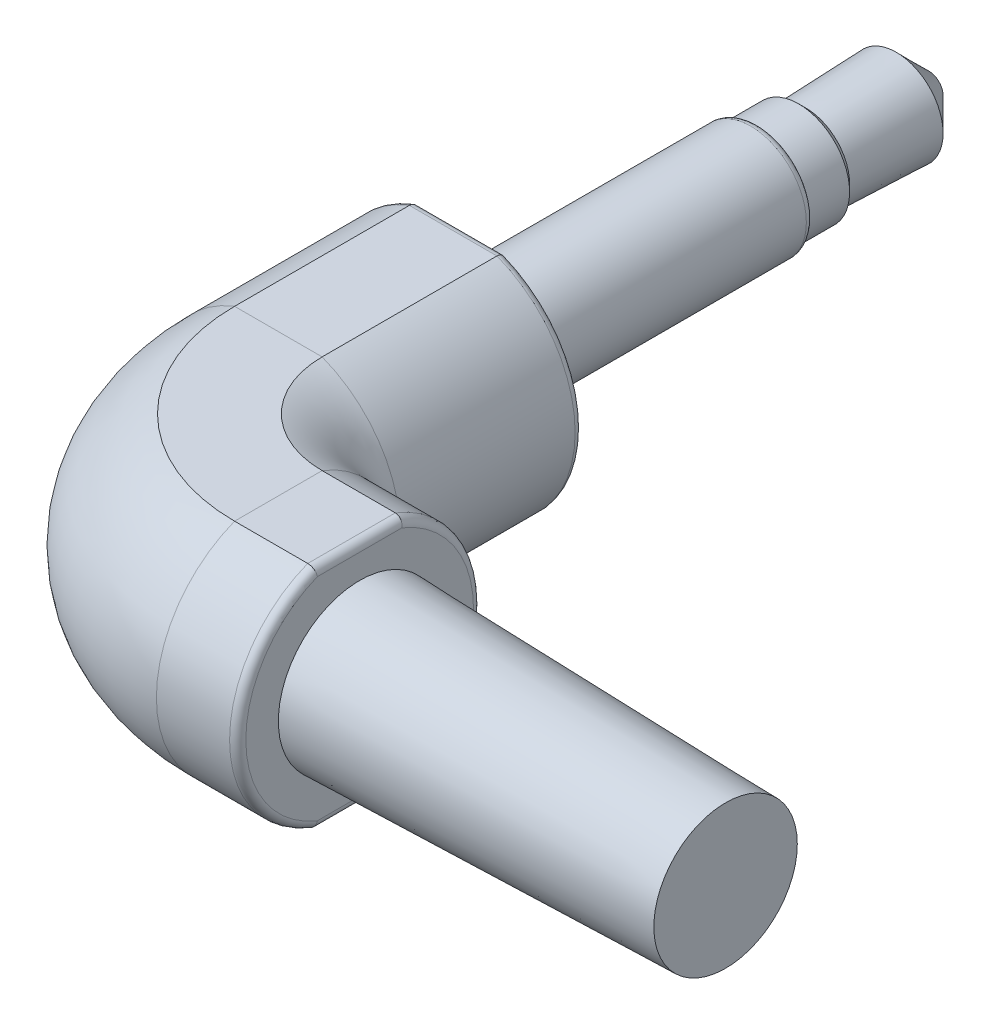
SolidWorks part; units mm, degrees
ref_plane "Front Plane" through (0, 0, 0) normal (0, 0, 1) x (1, 0, 0)
ref_plane "Top Plane" through (0, 0, 0) normal (0, 1, 0) x (1, 0, 0)
ref_plane "Right Plane" through (0, 0, 0) normal (1, 0, 0) x (0, 0, -1)
sketch "Sketch1" plane through (0, 0, 0) normal (0, 0, 1) x (1, 0, 0)
  circle A0 centre (0, 0) radius 1.4605
  dimension "D1" = 2.921
extrude "Boss-Extrude1" add sketch "Sketch1" against normal blind 14.605
chamfer "Chamfer1" distance 1.016 angle 45 1 edges at (1.4605, 0, -14.605)
sketch "Sketch4" plane through (0, 0, 0) normal (0, 1, 0) x (1, 0, 0)
  line L0 (1.4605, 13.589) -> (0.986, 0)
  line L1 (-1.4605, 0) -> (1.4605, 0) construction
  line L2 (0.986, 0) -> (2.0403, 0)
  line L3 (2.0403, 0) -> (2.0403, 13.589)
  line L4 (2.0403, 13.589) -> (1.4605, 13.589)
  line L5 (0, -1000) -> (0, 49000) construction
  dimension "D1" = 88
revolve "Cut-Revolve1" cut sketch "Sketch4" angle 360 about L5
sketch "Sketch2" plane through (0, 0, 0) normal (0, 0, 1) x (1, 0, 0)
  circle A0 centre (0, 0) radius 1.5875
  dimension "D1" = 3.175
extrude "Boss-Extrude2" add sketch "Sketch2" against normal blind 10.795
chamfer "Chamfer2" distance 0.254 angle 45 1 edges at (1.5875, 0, -10.795)
sketch "Sketch3" plane through (0, 0, 0) normal (0, 0, 1) x (1, 0, 0)
  circle A0 centre (0, 0) radius 1.7399
  dimension "D1" = 3.4798
extrude "Boss-Extrude3" add sketch "Sketch3" against normal blind 9.271
fillet "Fillet1" radius 0.254 1 edges at (1.7399, 0, -9.271)
sketch "Sketch5" plane through (0, 0, 0) normal (0, 0, 1) x (1, 0, 0)
  circle A0 centre (0, 0) radius 2.2225
  dimension "D1" = 4.445
extrude "Boss-Extrude4" add sketch "Sketch5" against normal blind 0.762
sketch "Sketch6" plane through (0, 0, 0) normal (0, 0, 1) x (1, 0, 0)
  line L0 (-1.3678, 3.556) -> (1.3678, 3.556)
  line L1 (-1.3678, -3.556) -> (1.3678, -3.556)
  arc A0 (-1.3678, 3.556) -> (-1.3678, -3.556) centre (0, 0) ccw
  arc A1 (1.3678, -3.556) -> (1.3678, 3.556) centre (0, 0) ccw
  dimension "D1" = 7.62
  dimension "D2" = 7.112
  dimension "D3" = 3.556
sketch "Sketch7" plane through (0, 0, 0) normal (0, 1, 0) x (1, 0, 0)
  line L0 (0, 0) -> (0, -5.715)
  line L1 (4.445, -10.16) -> (6.985, -10.16)
  arc A0 (0, -5.715) -> (4.445, -10.16) centre (4.445, -5.715) ccw
  dimension "D1" = 4.445
  dimension "D2" = 10.16
  dimension "D3" = 6.985
sweep "Sweep2" add profiles "Sketch6" path "Sketch7"
sketch "Sketch8" plane through (6.985, 0, 0) normal (1, 0, 0) x (0, 0, -1)
  circle A0 centre (-10.16, 0) radius 2.54
  dimension "D1" = 5.08
extrude "Boss-Extrude5" add sketch "Sketch8" along normal blind 11.43 draft 1.5
fillet "Fillet2" radius 0.254 8 edges at (6.985, -3.556, 10.16) (6.985, 3.556, 10.16) (6.985, 0, 6.35) (6.985, 0, 13.97) (0, 3.556, 0) (-3.81, 0, 0) (0, -3.556, 0) (3.81, 0, 0)
